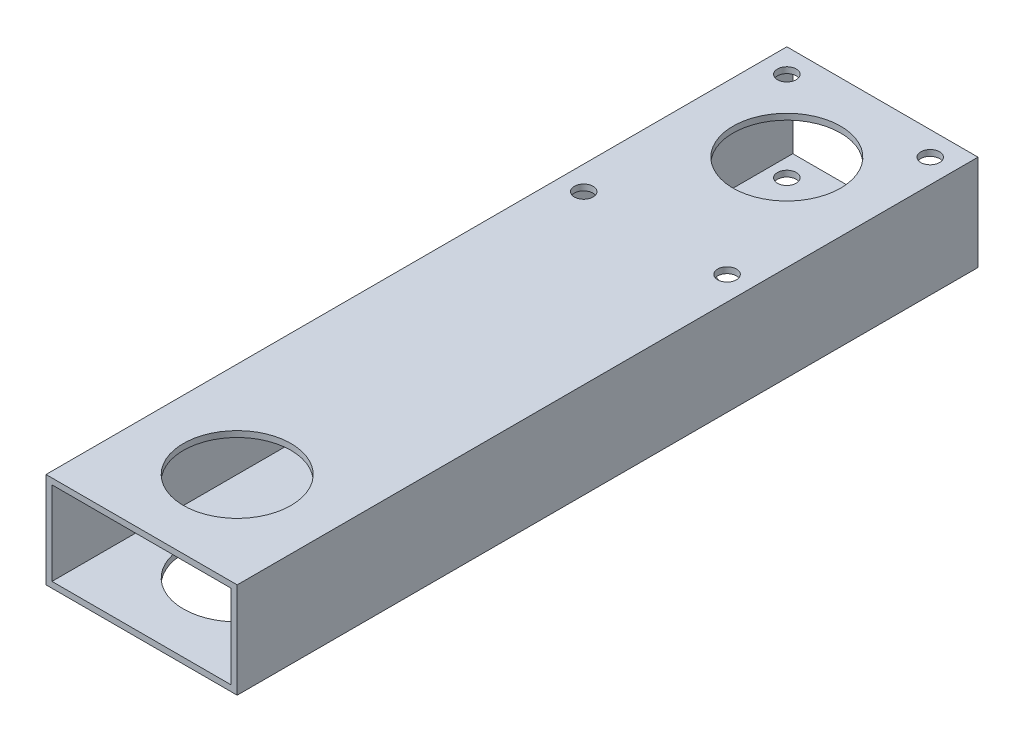
SolidWorks part; units mm, degrees
material "6061 Alloy"
ref_plane "Front Plane" through (0, 0, 0) normal (0, 0, 1) x (1, 0, 0)
ref_plane "Top Plane" through (0, 0, 0) normal (0, 1, 0) x (1, 0, 0)
ref_plane "Right Plane" through (0, 0, 0) normal (1, 0, 0) x (0, 0, -1)
sketch "Sketch1" plane through (0, 0, 0) normal (0, 0, 1) x (1, 0, 0)
  line L0 (-23.8125, 11.1125) -> (23.8125, 11.1125)
  line L2 (-25.4, 12.7) -> (25.4, 12.7)
  line L3 (-25.4, 12.7) -> (-25.4, -12.7)
  line L4 (-25.4, -12.7) -> (25.4, -12.7)
  line L5 (25.4, 12.7) -> (25.4, -12.7)
  line L10 (23.8125, 11.1125) -> (23.8125, -11.1125)
  line L11 (-23.8125, -11.1125) -> (23.8125, -11.1125)
  line L12 (-23.8125, 11.1125) -> (-23.8125, -11.1125)
  point P12 (0, 12.7)
  point P14 (25.4, 0)
  dimension "Wall Thickness" = 1.5875
  dimension "Outside Width" = 50.8
  dimension "Outside Height" = 25.4
  dimension "Inside Height" = 22.225
  dimension "Inside Width" = 47.625
sketch "Sketch2" plane through (0, 0, 0) normal (1, 0, 0) x (0, 0, -1)
  line L0 (98.425, 0) -> (-98.425, 0)
  point P4 (0, 0)
  point P7 (-98.425, 0)
  point P10 (98.425, 0)
  dimension "Length" = 196.85
sketch "Sketch3" plane through (0, 0, 0) normal (0, 0, 1) x (1, 0, 0)
  line L21 (25.4, 12.7) -> (-25.4, 12.7)
  line L22 (25.4, -12.7) -> (25.4, 12.7)
  line L23 (-25.4, -12.7) -> (25.4, -12.7)
  line L24 (-25.4, 12.7) -> (-25.4, -12.7)
  line L25 (25.4, 12.7) -> (-25.4, 12.7)
  line L26 (25.4, -12.7) -> (25.4, 12.7)
  line L27 (-25.4, -12.7) -> (25.4, -12.7)
  line L28 (-25.4, 12.7) -> (-25.4, -12.7)
  line L29 (23.8125, 11.1125) -> (-23.8125, 11.1125)
  line L30 (23.8125, -11.1125) -> (23.8125, 11.1125)
  line L31 (-23.8125, -11.1125) -> (23.8125, -11.1125)
  line L32 (-23.8125, 11.1125) -> (-23.8125, -11.1125)
  line L33 (23.8125, 11.1125) -> (-23.8125, 11.1125)
  line L34 (23.8125, -11.1125) -> (23.8125, 11.1125)
  line L35 (-23.8125, -11.1125) -> (23.8125, -11.1125)
  line L36 (-23.8125, 11.1125) -> (-23.8125, -11.1125)
  dimension "D1" = 0
  dimension "D2" = 0
extrude "Boss-Extrude1" add sketch "Sketch3" along normal up to vertex (98.425 mm away) and the other way up to vertex (98.425 mm away) up to point (0, 0, 98.425) other way up to point (0, 0, -98.425)
sketch "Drawing Reference" plane through (0, 0, 0) normal (1, 0, 0) x (0, 0, -1)
  line L0 (-98.425, 0) -> (98.425, 0) construction
  line L1 (0, -12.7) -> (0, 12.7) construction
  line L2 (-98.425, -12.7) -> (98.425, -12.7) construction
  line L5 (-98.425, 12.7) -> (98.425, 12.7) construction
  point P7 (-61.849, 0)
  point P8 (61.849, 0)
  dimension "D1" = 36.576
sketch "Sketch4" plane through (0, -12.7, 0) normal (0, -1, 0) x (1, 0, 0)
  line L0 (-25.4, 0) -> (0, 0) construction
  line L1 (-25.4, 98.425) -> (-25.4, -98.425) construction
  line L2 (0, 0) -> (0, -73.025) construction
  line L3 (0, 0) -> (0, 73.025) construction
  circle A0 centre (0, 73.025) radius 14.2875
  circle A1 centre (0, -73.025) radius 14.2875
extrude "Cut-Extrude3" cut sketch "Sketch4" against normal through all
hole_wizard "#10 Clearance Hole1" positions "Sketch5" profile "Sketch6" hole size "#10" standard "ANSI Inch" end condition through all
sketch "Sketch5" plane through (0, 12.7, 0) normal (0, 1, 0) x (1, 0, 0)
  point P0 (19.05, 38.1)
  point P3 (19.05, 92.075)
  point P6 (-19.05, 92.075)
  point P9 (-19.05, 38.1)
sketch "Sketch6" plane through (19.05, 12.7, -38.1) normal (1, 0, 0) x (0, 0, 1)
  line L0 (0, 0) -> (0, 25.4)
  line L1 (0, 25.4) -> (2.4892, 25.4)
  line L2 (2.4892, 25.4) -> (2.4892, 0)
  line L5 (2.4892, 0) -> (0, 0)
  line L11 (0, -6.35) -> (0, 107.95) construction
  dimension "Thru Hole Dia." = 4.9784
  dimension "Thru Hole Depth" = 25.4
equation "\"D1@Drawing Reference\"=\"Outside Width@Sketch1\" * 0.72"
